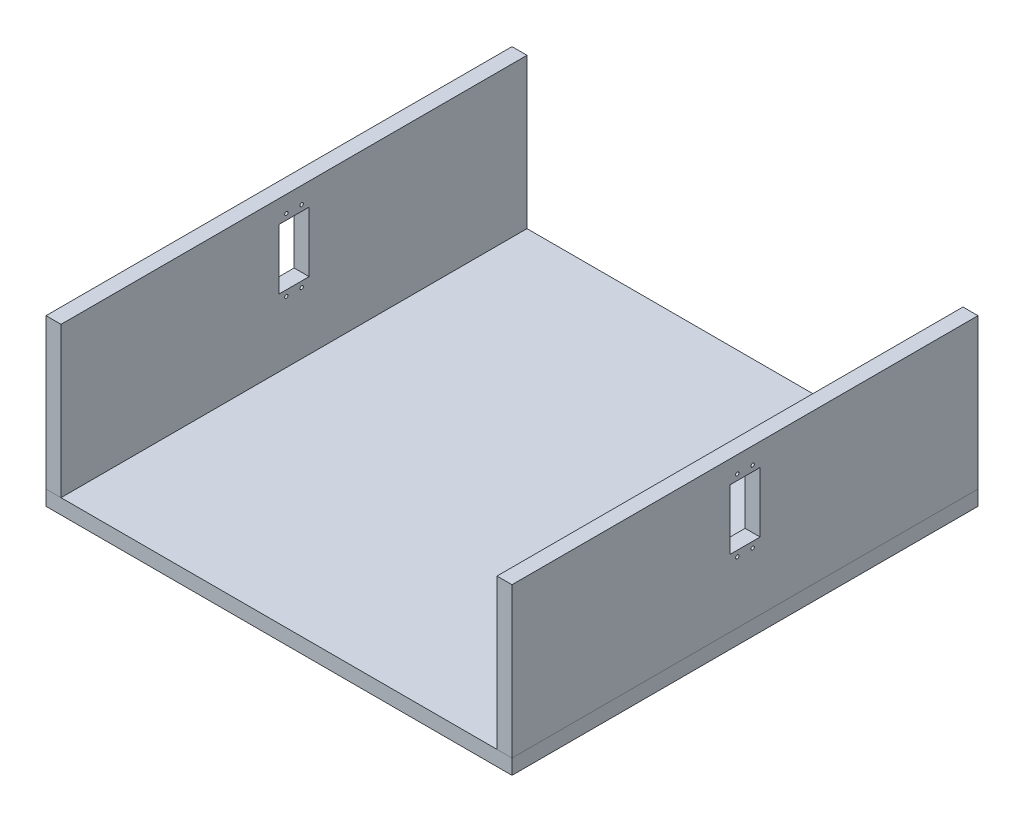
SolidWorks part; units mm, degrees
ref_plane "Front Plane" through (0, 0, 0) normal (0, 0, 1) x (1, 0, 0)
ref_plane "Top Plane" through (0, 0, 0) normal (0, 1, 0) x (1, 0, 0)
ref_plane "Right Plane" through (0, 0, 0) normal (1, 0, 0) x (0, 0, -1)
sketch "Sketch1" plane through (0, 0, 0) normal (0, 1, 0) x (1, 0, 0)
  line L1 (-155.2, -155.2) -> (155.2, -155.2)
  line L2 (-155.2, -155.2) -> (-155.2, 155.2)
  line L3 (-155.2, 155.2) -> (155.2, 155.2)
  line L4 (155.2, -155.2) -> (155.2, 155.2)
  line L5 (-155.2, -155.2) -> (155.2, 155.2) construction
  line L6 (-155.2, 155.2) -> (155.2, -155.2) construction
  point P0 (0, 0)
  dimension "D2" = 310.4
extrude "Boss-Extrude1" add sketch "Sketch1" along normal blind 10
sketch "Sketch3" plane through (0, 10, 0) normal (0, 1, 0) x (1, 0, 0)
  line L0 (155.2, 155.2) -> (-155.2, 155.2) construction
  line L1 (155.2, 155.2) -> (145.2, 155.2)
  line L2 (155.2, 155.2) -> (155.2, -155.2)
  line L3 (155.2, -155.2) -> (145.2, -155.2)
  line L4 (145.2, 155.2) -> (145.2, -155.2)
  line L5 (155.2, -155.2) -> (155.2, 155.2) construction
  line L6 (-155.2, -155.2) -> (155.2, -155.2) construction
  line L12 (-155.2, 155.2) -> (-145.2, 155.2)
  line L13 (-155.2, 155.2) -> (-155.2, -155.2)
  line L14 (-155.2, -155.2) -> (-145.2, -155.2)
  line L15 (-145.2, 155.2) -> (-145.2, -155.2)
  dimension "D1" = 10
  dimension "D2" = 10
extrude "Boss-Extrude2" add sketch "Sketch3" along normal blind 100
sketch "Sketch4" plane through (155.2, 0, 0) normal (1, 0, 0) x (0, 0, -1)
  line L1 (-155.2, 110) -> (155.2, 110) construction
  line L3 (-10.06, 54.88) -> (10.06, 54.88)
  line L4 (-10.06, 54.88) -> (-10.06, 95)
  line L5 (-10.06, 95) -> (10.06, 95)
  line L6 (10.06, 54.88) -> (10.06, 95)
  line L7 (-10.06, 54.88) -> (10.06, 95) construction
  line L8 (-10.06, 95) -> (10.06, 54.88) construction
  point P0 (0, 74.94)
  point P8 (0, 110)
  dimension "D1" = 20.12
  dimension "D2" = 40.12
  dimension "D3" = 15
extrude "Cut-Extrude2" cut sketch "Sketch4" against normal through all
sketch "Sketch5" plane through (155.2, 0, 0) normal (1, 0, 0) x (0, 0, -1)
  line L3 (10.06, 54.88) -> (10.06, 95) construction
  line L5 (10.06, 95) -> (-10.06, 95) construction
  circle A1 centre (5.1, 98.84) radius 1.125
  circle A2 centre (-5.1, 98.84) radius 1.125
  circle A3 centre (-5.1, 51.04) radius 1.125
  circle A4 centre (5.1, 51.04) radius 1.125
  point P8 (0, 0)
  point P9 (0, 0)
  point P10 (0, 0)
  point P11 (0, 0)
  point P12 (0, 0)
  point P17 (0, 95)
  point P18 (10.06, 74.94)
  dimension "D1" = 10.2
  dimension "D5" = 2.25
  dimension "D2" = 47.8
  dimension "D3" = 23.9
  dimension "D4" = 5.1
extrude "Cut-Extrude3" cut sketch "Sketch5" against normal through all
